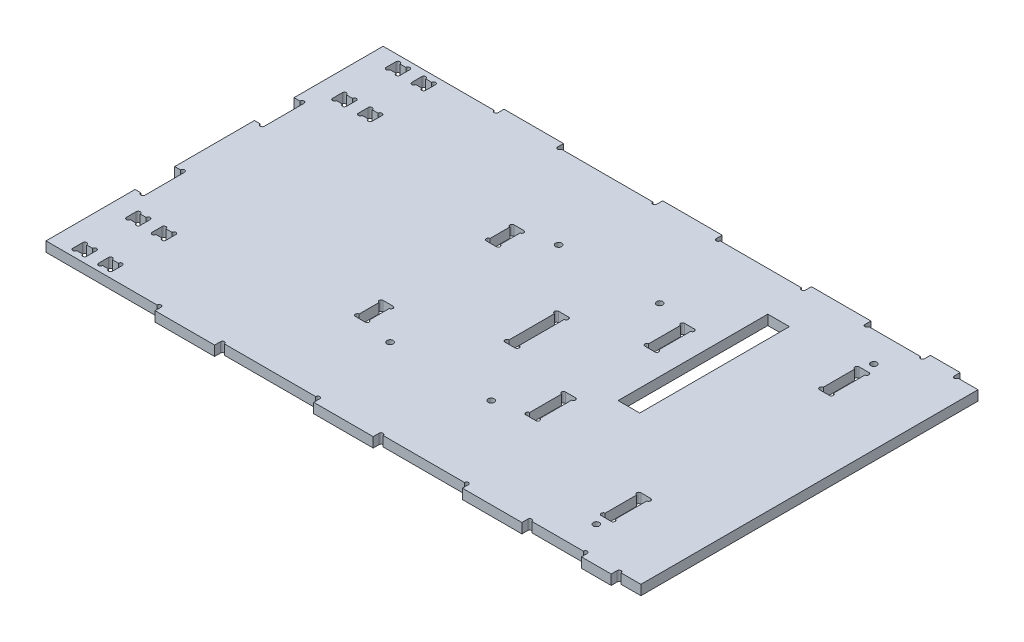
SolidWorks part; units mm, degrees
ref_plane "정면" through (0, 0, 0) normal (0, 0, 1) x (1, 0, 0)
ref_plane "윗면" through (0, 0, 0) normal (0, 1, 0) x (1, 0, 0)
ref_plane "우측면" through (0, 0, 0) normal (1, 0, 0) x (0, 0, -1)
sketch "스케치1" plane through (0, 0, 0) normal (0, 1, 0) x (1, 0, 0)
  line L1 (0, 0) -> (300, 0)
  line L2 (0, 0) -> (0, 170)
  line L3 (0, 170) -> (300, 170)
  line L4 (300, 0) -> (300, 170)
  dimension "D1" = 170
  dimension "D2" = 300
extrude "보스-돌출1" add sketch "스케치1" along normal blind 5
sketch "스케치2" plane through (0, 0, 0) normal (0, -1, 0) x (1, 0, 0)
  line L0 (160, -71.5) -> (160, 0) construction
  line L1 (160, -71.5) -> (165, -71.5)
  line L2 (160, -71.5) -> (160, -98.5)
  line L3 (160, -98.5) -> (165, -98.5)
  line L4 (165, -71.5) -> (165, -98.5)
  line L5 (0, 0) -> (300, 0) construction
  line L6 (160, -98.5) -> (160, -170) construction
  line L7 (300, -170) -> (0, -170) construction
  line L10 (300, 0) -> (300, -170) construction
  line L11 (260, 0) -> (260, -20) construction
  line L12 (260, -20) -> (265, -20)
  line L13 (260, -20) -> (260, -40)
  line L14 (260, -40) -> (265, -40)
  line L15 (265, -20) -> (265, -40)
  line L16 (260, -130) -> (265, -130)
  line L17 (260, -130) -> (260, -150)
  line L18 (260, -150) -> (265, -150)
  line L19 (265, -130) -> (265, -150)
  line L20 (260, -40) -> (260, -130) construction
  line L21 (260, -150) -> (260, -170) construction
  line L22 (265, -130) -> (265, -40) construction
  dimension "D1" = 27
  dimension "D2" = 140
  dimension "D3" = 5
  dimension "D4" = 20
  dimension "D5" = 20
  dimension "D6" = 40
  dimension "D7" = 5
extrude "컷-돌출1" cut sketch "스케치2" against normal blind 10
sketch "스케치3" plane through (0, 5, 0) normal (0, 1, 0) x (1, 0, 0)
  line L0 (183.55, 42.5) -> (180.45, 42.5) construction
  line L1 (183.55, 40) -> (183.55, 45) construction
  line L2 (180.45, 40) -> (180.45, 45) construction
  line L3 (180.45, 42.5) -> (132.55, 42.5) construction
  line L4 (132.55, 40) -> (132.55, 45) construction
  line L5 (132.55, 42.5) -> (129.45, 42.5) construction
  line L6 (129.45, 40) -> (129.45, 45) construction
  line L7 (183.55, 127.5) -> (180.45, 127.5) construction
  line L8 (183.55, 125) -> (183.55, 130) construction
  line L9 (180.45, 125) -> (180.45, 130) construction
  line L10 (180.45, 127.5) -> (132.55, 127.5) construction
  line L11 (132.55, 125) -> (132.55, 130) construction
  line L12 (132.55, 127.5) -> (129.45, 127.5) construction
  line L13 (129.45, 125) -> (129.45, 130) construction
  line L18 (262.5, 16.55) -> (262.5, 13.45) construction
  line L19 (265, 16.55) -> (260, 16.55) construction
  line L20 (265, 13.45) -> (260, 13.45) construction
  line L25 (262.5, 156.55) -> (262.5, 153.45) construction
  line L26 (265, 156.55) -> (260, 156.55) construction
  line L27 (265, 153.45) -> (260, 153.45) construction
  circle A0 centre (131, 127.5) radius 1.55
  circle A1 centre (182, 127.5) radius 1.55
  circle A2 centre (182, 42.5) radius 1.55
  circle A3 centre (131, 42.5) radius 1.55
  circle A8 centre (262.5, 155) radius 1.55
  circle A10 centre (262.5, 15) radius 1.55
  dimension "D1" = 3.1
extrude "컷-돌출2" cut sketch "스케치3" against normal blind 10
sketch "스케치4" plane through (0, 0, 0) normal (0, -1, 0) x (1, 0, 0)
  line L0 (5, -64.8) -> (0, -64.8) construction
  line L1 (5, -45) -> (0, -45) construction
  line L2 (0, -85) -> (51.0766, -85) construction
  line L3 (0, -170) -> (0, 0) construction
  line L4 (5, -105.1) -> (5, -125.1)
  line L5 (0, -64.9) -> (5, -64.9)
  line L6 (0, -64.9) -> (0, -44.9)
  line L7 (0, -44.9) -> (5, -44.9)
  line L8 (5, -64.9) -> (5, -44.9)
  line L9 (0, -125.1) -> (5, -125.1)
  line L10 (0, -105.1) -> (0, -125.1)
  line L11 (0, -105.1) -> (5, -105.1)
  dimension "D1" = 0.1
  dimension "D2" = 0.1
  dimension "D3" = 5
extrude "컷-돌출3" cut sketch "스케치4" against normal blind 5
sketch "스케치5" plane through (0, 0, 0) normal (0, -1, 0) x (1, 0, 0)
  line L0 (160, -71.5) -> (160, -98.5) construction
  line L1 (165, -98.5) -> (165, -71.5) construction
  line L2 (5, -44.9) -> (0, -44.9) construction
  line L3 (0, -64.9) -> (5, -64.9) construction
  line L12 (260, -20) -> (260, -40) construction
  line L13 (265, -40) -> (265, -20) construction
  line L14 (300, -85) -> (0, -85) construction
  line L15 (300, 0) -> (300, -170) construction
  line L16 (0, -105.1) -> (0, -64.9) construction
  circle A0 centre (160, -72.55) radius 1.05
  circle A1 centre (3.95, -44.9) radius 1.05
  circle A2 centre (3.95, -64.9) radius 1.05
  circle A3 centre (165, -72.55) radius 1.05
  circle A4 centre (260, -21.05) radius 1.05
  circle A5 centre (265, -38.95) radius 1.05
  circle A6 centre (260, -38.95) radius 1.05
  circle A7 centre (265, -21.05) radius 1.05
  circle A8 centre (265, -148.95) radius 1.05
  circle A9 centre (260, -131.05) radius 1.05
  circle A10 centre (265, -131.05) radius 1.05
  circle A11 centre (260, -148.95) radius 1.05
  circle A12 centre (165, -97.45) radius 1.05
  circle A13 centre (3.95, -105.1) radius 1.05
  circle A14 centre (3.95, -125.1) radius 1.05
  circle A15 centre (160, -97.45) radius 1.05
  dimension "D1" = 2.1
extrude "컷-돌출4" cut sketch "스케치5" against normal blind 10
sketch "스케치8" plane through (0, 0, 0) normal (0, -1, 0) x (1, 0, 0)
  line L0 (0, 0) -> (300, 0) construction
  line L1 (58, 0) -> (88, 0)
  line L2 (58, 0) -> (58, 3)
  line L3 (58, 3) -> (88, 3)
  line L4 (88, 0) -> (88, 3)
  line L5 (0, 3) -> (57.9, 3) construction
  line L6 (0, 0) -> (300, 0) construction
  line L7 (138, 3) -> (168, 3)
  line L8 (138, 3) -> (138, 0)
  line L9 (138, 0) -> (168, 0)
  line L10 (168, 3) -> (168, 0)
  line L11 (0, 0) -> (300, 0) construction
  line L12 (213, 3) -> (243, 3)
  line L13 (213, 3) -> (213, 0)
  line L14 (213, 0) -> (243, 0)
  line L15 (243, 3) -> (243, 0)
  line L16 (0, 0) -> (300, 0) construction
  line L17 (273, 3) -> (288, 3)
  line L18 (273, 3) -> (273, 0)
  line L19 (273, 0) -> (288, 0)
  line L20 (288, 3) -> (288, 0)
  line L21 (300, 0) -> (300, -170) construction
  line L22 (0, -85) -> (300, -85) construction
  line L23 (0, -105.1) -> (0, -64.9) construction
  line L24 (288, -173) -> (288, -170)
  line L25 (273, -170) -> (288, -170)
  line L26 (273, -173) -> (273, -170)
  line L27 (273, -173) -> (288, -173)
  line L28 (243, -173) -> (243, -170)
  line L29 (213, -170) -> (243, -170)
  line L30 (213, -173) -> (213, -170)
  line L31 (213, -173) -> (243, -173)
  line L32 (168, -173) -> (168, -170)
  line L33 (138, -170) -> (168, -170)
  line L34 (138, -173) -> (138, -170)
  line L35 (138, -173) -> (168, -173)
  line L36 (88, -170) -> (88, -173)
  line L37 (58, -173) -> (88, -173)
  line L38 (58, -170) -> (58, -173)
  line L39 (58, -170) -> (88, -170)
  dimension "D1" = 12
  dimension "D2" = 15
  dimension "D3" = 30
  dimension "D4" = 30
  dimension "D5" = 45
  dimension "D6" = 30
  dimension "D7" = 50
  dimension "D8" = 30
extrude "보스-돌출2" add sketch "스케치8" against normal blind 5
sketch "스케치9" plane through (0, 0, 0) normal (0, -1, 0) x (1, 0, 0)
  line L0 (0, 0) -> (58, 0) construction
  line L1 (88, 0) -> (138, 0) construction
  line L2 (88, 0) -> (138, 0) construction
  line L3 (168, 0) -> (213, 0) construction
  line L4 (168, 0) -> (213, 0) construction
  line L5 (243, 0) -> (273, 0) construction
  line L6 (243, 0) -> (273, 0) construction
  line L7 (288, 0) -> (300, 0) construction
  line L8 (0, -85) -> (300, -85) construction
  line L9 (0, -105.1) -> (0, -64.9) construction
  line L10 (300, 0) -> (300, -170) construction
  circle A0 centre (57, 0) radius 1
  circle A1 centre (89, 0) radius 1
  circle A2 centre (137, 0) radius 1
  circle A3 centre (169, 0) radius 1
  circle A4 centre (212, 0) radius 1
  circle A5 centre (272, 0) radius 1
  circle A6 centre (244, 0) radius 1
  circle A7 centre (289, 0) radius 1
  circle A8 centre (289, -170) radius 1
  circle A9 centre (244, -170) radius 1
  circle A10 centre (272, -170) radius 1
  circle A11 centre (212, -170) radius 1
  circle A12 centre (169, -170) radius 1
  circle A13 centre (137, -170) radius 1
  circle A14 centre (89, -170) radius 1
  circle A15 centre (57, -170) radius 1
  dimension "D1" = 2
extrude "컷-돌출6" cut sketch "스케치9" against normal blind 5
sketch "스케치13" plane through (0, 5, 0) normal (0, 1, 0) x (1, 0, 0)
  line L0 (30, 8.5) -> (30, 30.5) construction
  line L1 (30, 8.5) -> (23, 8.5)
  line L2 (30, 8.5) -> (30, 3.5)
  line L3 (30, 3.5) -> (23, 3.5)
  line L4 (23, 8.5) -> (23, 3.5)
  line L5 (17, 8.5) -> (10, 8.5)
  line L6 (17, 8.5) -> (17, 3.5)
  line L7 (17, 3.5) -> (10, 3.5)
  line L8 (10, 8.5) -> (10, 3.5)
  line L9 (30, 19.5) -> (11.9274, 19.5) construction
  line L10 (10, 30.5) -> (10, 35.5)
  line L11 (17, 35.5) -> (10, 35.5)
  line L12 (17, 30.5) -> (17, 35.5)
  line L13 (17, 30.5) -> (10, 30.5)
  line L14 (23, 30.5) -> (23, 35.5)
  line L15 (30, 35.5) -> (23, 35.5)
  line L16 (30, 30.5) -> (30, 35.5)
  line L17 (30, 30.5) -> (23, 30.5)
  line L18 (0, 85) -> (49.672, 85) construction
  line L19 (0, 105.1) -> (0, 64.9) construction
  line L20 (30, 150.5) -> (11.9274, 150.5) construction
  line L21 (30, 161.5) -> (30, 139.5) construction
  line L22 (30, 139.5) -> (23, 139.5)
  line L23 (30, 139.5) -> (30, 134.5)
  line L24 (30, 134.5) -> (23, 134.5)
  line L25 (23, 139.5) -> (23, 134.5)
  line L26 (17, 139.5) -> (10, 139.5)
  line L27 (17, 139.5) -> (17, 134.5)
  line L28 (17, 134.5) -> (10, 134.5)
  line L29 (10, 139.5) -> (10, 134.5)
  line L30 (10, 161.5) -> (10, 166.5)
  line L31 (17, 166.5) -> (10, 166.5)
  line L32 (17, 161.5) -> (17, 166.5)
  line L33 (17, 161.5) -> (10, 161.5)
  line L34 (23, 161.5) -> (23, 166.5)
  line L35 (30, 166.5) -> (23, 166.5)
  line L36 (30, 161.5) -> (30, 166.5)
  line L37 (30, 161.5) -> (23, 161.5)
extrude "컷-돌출9" cut sketch "스케치13" against normal blind 10
sketch "스케치14" plane through (0, 0, 0) normal (0, -1, 0) x (1, 0, 0)
  line L0 (10, -8.5) -> (17, -8.5) construction
  line L1 (17, -3.5) -> (10, -3.5) construction
  line L2 (17, -30.5) -> (23, -30.5) construction
  line L3 (23, -30.5) -> (23, -8.5) construction
  line L4 (23, -8.5) -> (17, -8.5) construction
  line L5 (17, -8.5) -> (17, -30.5) construction
  line L6 (20, -30.5) -> (20, -8.5) construction
  line L7 (17, -19.5) -> (23, -19.5) construction
  line L8 (0, -85) -> (55.1733, -85) construction
  line L9 (0, -105.1) -> (0, -64.9) construction
  line L10 (17, -150.5) -> (23, -150.5) construction
  line L11 (20, -139.5) -> (20, -161.5) construction
  line L12 (17, -161.5) -> (17, -139.5) construction
  line L13 (23, -161.5) -> (17, -161.5) construction
  line L14 (23, -139.5) -> (23, -161.5) construction
  line L15 (17, -139.5) -> (23, -139.5) construction
  circle A0 centre (11, -8.5) radius 1
  circle A1 centre (11, -3.5) radius 1
  circle A2 centre (16, -3.5) radius 1
  circle A3 centre (16, -8.5) radius 1
  circle A4 centre (24, -8.5) radius 1
  circle A5 centre (24, -3.5) radius 1
  circle A6 centre (29, -3.5) radius 1
  circle A7 centre (29, -8.5) radius 1
  circle A8 centre (29, -30.5) radius 1
  circle A9 centre (29, -35.5) radius 1
  circle A10 centre (24, -35.5) radius 1
  circle A11 centre (24, -30.5) radius 1
  circle A12 centre (16, -30.5) radius 1
  circle A13 centre (16, -35.5) radius 1
  circle A14 centre (11, -35.5) radius 1
  circle A15 centre (11, -30.5) radius 1
  circle A16 centre (11, -139.5) radius 1
  circle A17 centre (11, -134.5) radius 1
  circle A18 centre (16, -134.5) radius 1
  circle A19 centre (16, -139.5) radius 1
  circle A20 centre (24, -139.5) radius 1
  circle A21 centre (24, -134.5) radius 1
  circle A22 centre (29, -134.5) radius 1
  circle A23 centre (29, -139.5) radius 1
  circle A24 centre (29, -161.5) radius 1
  circle A25 centre (29, -166.5) radius 1
  circle A26 centre (24, -166.5) radius 1
  circle A27 centre (24, -161.5) radius 1
  circle A28 centre (16, -161.5) radius 1
  circle A29 centre (16, -166.5) radius 1
  circle A30 centre (11, -166.5) radius 1
  circle A31 centre (11, -161.5) radius 1
  dimension "D1" = 2
extrude "컷-돌출10" cut sketch "스케치14" against normal blind 10
sketch "스케치15" plane through (0, 5, 0) normal (0, 1, 0) x (1, 0, 0)
  line L1 (111, 125) -> (116, 125)
  line L2 (111, 125) -> (111, 111)
  line L3 (111, 111) -> (116, 111)
  line L4 (116, 125) -> (116, 111)
  line L5 (111, 45) -> (116, 45)
  line L6 (111, 45) -> (111, 59)
  line L7 (111, 59) -> (116, 59)
  line L8 (116, 45) -> (116, 59)
  line L9 (197, 65) -> (202, 65)
  line L10 (197, 65) -> (197, 45)
  line L11 (197, 45) -> (202, 45)
  line L12 (202, 65) -> (202, 45)
  line L13 (197, 105) -> (202, 105)
  line L14 (197, 105) -> (197, 125)
  line L15 (197, 125) -> (202, 125)
  line L16 (202, 105) -> (202, 125)
  arc A0 (116, 56.5) -> (116, 59) centre (116, 57.75) ccw construction
  dimension "D1" = 5
extrude "컷-돌출11" cut sketch "스케치15" against normal blind 10
sketch "스케치16" plane through (0, 5, 0) normal (0, 1, 0) x (1, 0, 0)
  line L0 (111, 59) -> (111, 45) construction
  line L1 (116, 45) -> (116, 59) construction
  line L2 (111, 125) -> (111, 111) construction
  line L3 (116, 111) -> (116, 125) construction
  line L4 (202, 105) -> (202, 125) construction
  line L5 (197, 125) -> (197, 105) construction
  line L6 (197, 65) -> (197, 45) construction
  line L7 (202, 45) -> (202, 65) construction
  circle A0 centre (111, 46) radius 1
  circle A1 centre (116, 46) radius 1
  circle A2 centre (116, 58) radius 1
  circle A3 centre (111, 58) radius 1
  circle A4 centre (111, 112) radius 1
  circle A5 centre (116, 112) radius 1
  circle A6 centre (116, 124) radius 1
  circle A7 centre (111, 124) radius 1
  circle A8 centre (202, 124) radius 1
  circle A10 centre (197, 124) radius 1
  circle A11 centre (197, 64) radius 1
  circle A12 centre (202, 64) radius 1
  circle A13 centre (202, 106) radius 1
  circle A14 centre (197, 106) radius 1
  circle A15 centre (197, 46) radius 1
  circle A16 centre (202, 46) radius 1
  dimension "D1" = 2
extrude "컷-돌출12" cut sketch "스케치16" against normal blind 10
sketch "스케치17" plane through (0, 5, 0) normal (0, 1, 0) x (1, 0, 0)
  line L0 (219, 97.5569) -> (219, 95.1974) construction
  line L1 (214, 74.5) -> (224.9, 74.5)
  line L2 (214, 74.5) -> (214, 150)
  line L3 (214, 150) -> (224.9, 150)
  line L4 (224.9, 74.5) -> (224.9, 150)
  line L6 (219.9, 97.5569) -> (219.9, 95.1974) construction
  line L7 (2.5, -5.5) -> (297.5, -5.5) construction
  line L8 (211, 170) -> (170, 170) construction
  dimension "D1" = 5
  dimension "D2" = 5
  dimension "D3" = 80
  dimension "D4" = 20
extrude "컷-돌출13" cut sketch "스케치17" against normal blind 10
sketch "스케치7" plane through (0, 0, 0) normal (0, -1, 0) x (1, 0, 0)
  line L0 (115.0287, -170) -> (111.9287, -170)
  line L1 (115.0287, -162) -> (116.2287, -162)
  line L2 (115.0287, -159.2) -> (115.0287, -158)
  line L3 (111.9287, -159.2) -> (111.9287, -158)
  line L4 (111.9287, -159.2) -> (110.7287, -159.2)
  line L5 (111.9287, -170) -> (111.9287, -162)
  line L6 (110.7287, -162) -> (111.9287, -162)
  line L7 (115.0287, -170) -> (115.0287, -162)
  line L8 (116.2287, -159.2) -> (115.0287, -159.2)
  line L9 (115.0287, -159.2) -> (111.9287, -159.2) construction
  line L10 (115.0287, -159.2) -> (115.0287, -162) construction
  line L11 (111.9287, -162) -> (111.9287, -159.2) construction
  line L12 (115.0287, -158) -> (111.9287, -158) construction
  line L13 (113.4787, -158) -> (113.4787, -155.529) construction
  line L14 (110.7287, -159.2) -> (110.7287, -162) construction
  line L15 (116.2287, -162) -> (116.2287, -159.2) construction
  line L16 (115.0287, -162) -> (111.9287, -162) construction
  line L17 (185.0287, -170) -> (181.9287, -170)
  line L18 (185.0287, -162) -> (186.2287, -162)
  line L19 (185.0287, -159.2) -> (185.0287, -158)
  line L20 (181.9287, -159.2) -> (181.9287, -158)
  line L21 (181.9287, -159.2) -> (180.7287, -159.2)
  line L22 (181.9287, -170) -> (181.9287, -162)
  line L23 (180.7287, -162) -> (181.9287, -162)
  line L24 (185.0287, -170) -> (185.0287, -162)
  line L25 (186.2287, -159.2) -> (185.0287, -159.2)
  line L26 (185.0287, -159.2) -> (181.9287, -159.2) construction
  line L27 (185.0287, -159.2) -> (185.0287, -162) construction
  line L28 (181.9287, -162) -> (181.9287, -159.2) construction
  line L29 (185.0287, -158) -> (181.9287, -158) construction
  line L30 (45.0287, -159.2) -> (41.9287, -159.2) construction
  line L31 (45.0287, -159.2) -> (45.0287, -162) construction
  line L32 (41.9287, -162) -> (41.9287, -159.2) construction
  line L33 (45.0287, -158) -> (41.9287, -158) construction
  line L34 (43.4787, -158) -> (43.4787, -155.529) construction
  line L35 (183.4787, -158) -> (183.4787, -155.529) construction
  line L36 (180.7287, -159.2) -> (180.7287, -162) construction
  line L37 (186.2287, -162) -> (186.2287, -159.2) construction
  line L38 (185.0287, -162) -> (181.9287, -162) construction
  line L39 (255.0287, -170) -> (251.9287, -170)
  line L40 (255.0287, -162) -> (256.2287, -162)
  line L41 (255.0287, -159.2) -> (255.0287, -158)
  line L42 (251.9287, -159.2) -> (251.9287, -158)
  line L43 (251.9287, -159.2) -> (250.7287, -159.2)
  line L44 (251.9287, -170) -> (251.9287, -162)
  line L45 (250.7287, -162) -> (251.9287, -162)
  line L46 (255.0287, -170) -> (255.0287, -162)
  line L47 (256.2287, -159.2) -> (255.0287, -159.2)
  line L48 (255.0287, -159.2) -> (251.9287, -159.2) construction
  line L49 (255.0287, -159.2) -> (255.0287, -162) construction
  line L50 (251.9287, -162) -> (251.9287, -159.2) construction
  line L51 (255.0287, -158) -> (251.9287, -158) construction
  line L52 (253.4787, -158) -> (253.4787, -155.529) construction
  line L53 (250.7287, -159.2) -> (250.7287, -162) construction
  line L54 (256.2287, -162) -> (256.2287, -159.2) construction
  line L55 (255.0287, -162) -> (251.9287, -162) construction
  line L56 (45.0287, -8) -> (41.9287, -8) construction
  line L57 (46.2287, -8) -> (46.2287, -10.8) construction
  line L58 (40.7287, -10.8) -> (40.7287, -8) construction
  line L59 (255.0287, -8) -> (251.9287, -8) construction
  line L60 (256.2287, -8) -> (256.2287, -10.8) construction
  line L61 (250.7287, -10.8) -> (250.7287, -8) construction
  line L62 (253.4787, -12) -> (253.4787, -14.471) construction
  line L63 (255.0287, -12) -> (251.9287, -12) construction
  line L64 (251.9287, -8) -> (251.9287, -10.8) construction
  line L65 (255.0287, -10.8) -> (255.0287, -8) construction
  line L66 (255.0287, -10.8) -> (251.9287, -10.8) construction
  line L67 (185.0287, -8) -> (181.9287, -8) construction
  line L68 (186.2287, -8) -> (186.2287, -10.8) construction
  line L69 (40.7287, -159.2) -> (40.7287, -162) construction
  line L71 (180.7287, -10.8) -> (180.7287, -8) construction
  line L72 (183.4787, -12) -> (183.4787, -14.471) construction
  line L73 (43.4787, -12) -> (43.4787, -14.471) construction
  line L74 (45.0287, -12) -> (41.9287, -12) construction
  line L75 (0, -85) -> (300, -85) construction
  line L76 (0, -105.1) -> (0, -64.9) construction
  line L77 (300, 0) -> (300, -170) construction
  line L78 (46.2287, -162) -> (46.2287, -159.2) construction
  line L79 (45.0287, -162) -> (41.9287, -162) construction
  line L80 (41.9287, -8) -> (41.9287, -10.8) construction
  line L81 (45.0287, -10.8) -> (45.0287, -8) construction
  line L82 (45.0287, -10.8) -> (41.9287, -10.8) construction
  line L83 (185.0287, -12) -> (181.9287, -12) construction
  line L84 (181.9287, -8) -> (181.9287, -10.8) construction
  line L85 (185.0287, -10.8) -> (185.0287, -8) construction
  line L86 (185.0287, -10.8) -> (181.9287, -10.8) construction
  line L87 (115.0287, -8) -> (111.9287, -8) construction
  line L88 (116.2287, -8) -> (116.2287, -10.8) construction
  line L89 (110.7287, -10.8) -> (110.7287, -8) construction
  line L90 (113.4787, -12) -> (113.4787, -14.471) construction
  line L91 (115.0287, -12) -> (111.9287, -12) construction
  line L92 (111.9287, -8) -> (111.9287, -10.8) construction
  line L93 (115.0287, -10.8) -> (115.0287, -8) construction
  line L94 (115.0287, -10.8) -> (111.9287, -10.8) construction
  line L95 (46.2287, -10.8) -> (45.0287, -10.8)
  line L96 (45.0287, 0) -> (45.0287, -8)
  line L97 (45.0287, -170) -> (41.9287, -170)
  line L98 (45.0287, -162) -> (46.2287, -162)
  line L99 (45.0287, -159.2) -> (45.0287, -158)
  line L100 (41.9287, -159.2) -> (41.9287, -158)
  line L101 (41.9287, -159.2) -> (40.7287, -159.2)
  line L102 (41.9287, -170) -> (41.9287, -162)
  line L103 (40.7287, -162) -> (41.9287, -162)
  line L104 (45.0287, -170) -> (45.0287, -162)
  line L105 (46.2287, -159.2) -> (45.0287, -159.2)
  line L106 (325.0287, -170) -> (321.9287, -170) [skipped]
  line L107 (325.0287, -162) -> (326.2287, -162) [skipped]
  line L108 (325.0287, -159.2) -> (325.0287, -158) [skipped]
  line L109 (321.9287, -159.2) -> (321.9287, -158) [skipped]
  line L110 (321.9287, -159.2) -> (320.7287, -159.2) [skipped]
  line L111 (321.9287, -170) -> (321.9287, -162) [skipped]
  line L112 (320.7287, -162) -> (321.9287, -162) [skipped]
  line L113 (325.0287, -170) -> (325.0287, -162) [skipped]
  line L114 (326.2287, -159.2) -> (325.0287, -159.2) [skipped]
  line L115 (325.0287, -159.2) -> (321.9287, -159.2) construction
  line L116 (325.0287, -159.2) -> (325.0287, -162) construction
  line L117 (321.9287, -162) -> (321.9287, -159.2) construction
  line L118 (325.0287, -158) -> (321.9287, -158) construction
  line L119 (323.4787, -158) -> (323.4787, -155.529) construction
  line L120 (320.7287, -159.2) -> (320.7287, -162) construction
  line L121 (326.2287, -162) -> (326.2287, -159.2) construction
  line L122 (325.0287, -162) -> (321.9287, -162) construction
  line L123 (40.7287, -8) -> (41.9287, -8)
  line L124 (41.9287, 0) -> (41.9287, -8)
  line L125 (41.9287, -10.8) -> (40.7287, -10.8)
  line L126 (41.9287, -10.8) -> (41.9287, -12)
  line L127 (45.0287, -10.8) -> (45.0287, -12)
  line L128 (45.0287, -8) -> (46.2287, -8)
  line L129 (45.0287, 0) -> (41.9287, 0)
  line L130 (256.2287, -10.8) -> (255.0287, -10.8)
  line L131 (255.0287, 0) -> (255.0287, -8)
  line L132 (250.7287, -8) -> (251.9287, -8)
  line L133 (251.9287, 0) -> (251.9287, -8)
  line L134 (251.9287, -10.8) -> (250.7287, -10.8)
  line L135 (251.9287, -10.8) -> (251.9287, -12)
  line L136 (255.0287, -10.8) -> (255.0287, -12)
  line L137 (255.0287, -8) -> (256.2287, -8)
  line L138 (255.0287, 0) -> (251.9287, 0)
  line L139 (186.2287, -10.8) -> (185.0287, -10.8)
  line L140 (185.0287, 0) -> (185.0287, -8)
  line L141 (180.7287, -8) -> (181.9287, -8)
  line L142 (181.9287, 0) -> (181.9287, -8)
  line L143 (181.9287, -10.8) -> (180.7287, -10.8)
  line L144 (181.9287, -10.8) -> (181.9287, -12)
  line L145 (185.0287, -10.8) -> (185.0287, -12)
  line L146 (185.0287, -8) -> (186.2287, -8)
  line L147 (185.0287, 0) -> (181.9287, 0)
  line L148 (116.2287, -10.8) -> (115.0287, -10.8)
  line L149 (115.0287, 0) -> (115.0287, -8)
  line L150 (110.7287, -8) -> (111.9287, -8)
  line L151 (111.9287, 0) -> (111.9287, -8)
  line L152 (111.9287, -10.8) -> (110.7287, -10.8)
  line L153 (111.9287, -10.8) -> (111.9287, -12)
  line L154 (115.0287, -10.8) -> (115.0287, -12)
  line L155 (115.0287, -8) -> (116.2287, -8)
  line L156 (115.0287, 0) -> (111.9287, 0)
  arc A0 (111.9287, -158) -> (115.0287, -158) centre (113.4787, -158) cw
  arc A1 (116.2287, -159.2) -> (116.2287, -162) centre (116.2287, -160.6) cw
  arc A2 (110.7287, -162) -> (110.7287, -159.2) centre (110.7287, -160.6) cw
  arc A3 (181.9287, -158) -> (185.0287, -158) centre (183.4787, -158) cw
  arc A4 (186.2287, -159.2) -> (186.2287, -162) centre (186.2287, -160.6) cw
  arc A5 (180.7287, -162) -> (180.7287, -159.2) centre (180.7287, -160.6) cw
  arc A6 (251.9287, -158) -> (255.0287, -158) centre (253.4787, -158) cw
  arc A7 (256.2287, -159.2) -> (256.2287, -162) centre (256.2287, -160.6) cw
  arc A8 (250.7287, -162) -> (250.7287, -159.2) centre (250.7287, -160.6) cw
  arc A9 (40.7287, -8) -> (40.7287, -10.8) centre (40.7287, -9.4) ccw
  arc A10 (46.2287, -10.8) -> (46.2287, -8) centre (46.2287, -9.4) ccw
  arc A11 (41.9287, -12) -> (45.0287, -12) centre (43.4787, -12) ccw
  arc A12 (250.7287, -8) -> (250.7287, -10.8) centre (250.7287, -9.4) ccw
  arc A13 (41.9287, -158) -> (45.0287, -158) centre (43.4787, -158) cw
  arc A14 (46.2287, -159.2) -> (46.2287, -162) centre (46.2287, -160.6) cw
  arc A15 (40.7287, -162) -> (40.7287, -159.2) centre (40.7287, -160.6) cw
  arc A16 (321.9287, -158) -> (325.0287, -158) centre (323.4787, -158) cw [skipped]
  arc A17 (326.2287, -159.2) -> (326.2287, -162) centre (326.2287, -160.6) cw [skipped]
  arc A18 (320.7287, -162) -> (320.7287, -159.2) centre (320.7287, -160.6) cw [skipped]
  arc A19 (256.2287, -10.8) -> (256.2287, -8) centre (256.2287, -9.4) ccw
  arc A20 (251.9287, -12) -> (255.0287, -12) centre (253.4787, -12) ccw
  arc A21 (180.7287, -8) -> (180.7287, -10.8) centre (180.7287, -9.4) ccw
  arc A22 (186.2287, -10.8) -> (186.2287, -8) centre (186.2287, -9.4) ccw
  arc A23 (181.9287, -12) -> (185.0287, -12) centre (183.4787, -12) ccw
  arc A24 (110.7287, -8) -> (110.7287, -10.8) centre (110.7287, -9.4) ccw
  arc A25 (116.2287, -10.8) -> (116.2287, -8) centre (116.2287, -9.4) ccw
  arc A26 (111.9287, -12) -> (115.0287, -12) centre (113.4787, -12) ccw
  dimension "D1" = 5
  dimension "D2" = 8
extrude "컷-돌출5" [suppressed] cut sketch "스케치7" against normal blind 10
sketch "스케치18" plane through (0, 0, 0) normal (0, -1, 0) x (1, 0, 0)
  line L0 (0, -85) -> (300, -85) construction
  line L1 (0, -105.1) -> (0, -64.9) construction
  line L2 (300, 0) -> (300, -170) construction
  line L4 (285, -152.5) -> (15, -152.5) construction
  line L5 (285, -152.5) -> (285, -17.5) construction
  line L6 (285, -17.5) -> (15, -17.5) construction
  line L7 (15, -152.5) -> (15, -17.5) construction
  line L8 (285, -152.5) -> (15, -17.5) construction
  line L9 (285, -17.5) -> (15, -152.5) construction
  circle A0 centre (15, -17.5) radius 6
  circle A1 centre (15, -152.5) radius 6
  circle A2 centre (285, -17.5) radius 6
  circle A3 centre (285, -152.5) radius 6
  point P6 (150, -85)
  dimension "D3" = 12
  dimension "D1" = 135
  dimension "D2" = 270
extrude "컷-돌출14" [suppressed] cut sketch "스케치18" against normal blind 1.5
sketch "스케치19" plane through (0, 5, 0) normal (0, 1, 0) x (1, 0, 0)
  line L0 (111, 123) -> (111, 113) construction
  line L1 (110.9, 123.914) -> (116.1, 123.914)
  line L2 (110.9, 123.914) -> (110.9, 112.1352)
  line L3 (110.9, 112.1352) -> (116.1, 112.1352)
  line L4 (116.1, 123.914) -> (116.1, 112.1352)
  line L5 (110.9, 57.988) -> (116.1, 57.988)
  line L6 (110.9, 57.988) -> (110.9, 46.2932)
  line L7 (110.9, 46.2932) -> (116.1, 46.2932)
  line L8 (116.1, 57.988) -> (116.1, 46.2932)
  line L9 (196.9, 63.9937) -> (202.1, 63.9937)
  line L10 (196.9, 63.9937) -> (196.9, 46.6181)
  line L11 (196.9, 46.6181) -> (202.1, 46.6181)
  line L12 (202.1, 63.9937) -> (202.1, 46.6181)
  line L13 (196.9, 123.914) -> (202.1, 123.914)
  line L14 (196.9, 123.914) -> (196.9, 106.2522)
  line L15 (196.9, 106.2522) -> (202.1, 106.2522)
  line L16 (202.1, 123.914) -> (202.1, 106.2522)
  line L17 (116, 113) -> (116, 123) construction
  line L18 (111, 57) -> (111, 47) construction
  line L19 (116, 47) -> (116, 57) construction
  line L20 (197, 63) -> (197, 47) construction
  line L21 (202, 47) -> (202, 63) construction
  line L22 (197, 123) -> (197, 107) construction
  line L23 (202, 107) -> (202, 123) construction
  line L24 (260, 132.1) -> (260, 147.9) construction
  line L25 (259.9, 21.181) -> (265.1, 21.181)
  line L26 (259.9, 21.181) -> (259.9, 38.6155)
  line L27 (259.9, 38.6155) -> (265.1, 38.6155)
  line L28 (265.1, 21.181) -> (265.1, 38.6155)
  line L29 (259.9, 131.2347) -> (265.1, 131.2347)
  line L30 (259.9, 131.2347) -> (259.9, 149.0422)
  line L31 (259.9, 149.0422) -> (265.1, 149.0422)
  line L32 (265.1, 131.2347) -> (265.1, 149.0422)
  line L33 (265, 147.9) -> (265, 132.1) construction
  line L34 (260, 22.1) -> (260, 37.9) construction
  line L35 (265, 37.9) -> (265, 22.1) construction
  dimension "D1" = 0.1
  dimension "D2" = 0.1
  dimension "D3" = 0.1
  dimension "D4" = 0.1
  dimension "D5" = 0.1
  dimension "D6" = 0.1
  dimension "D7" = 0.1
  dimension "D8" = 0.1
  dimension "D9" = 0.1
  dimension "D10" = 0.1
  dimension "D11" = 0.1
  dimension "D12" = 0.1
extrude "컷-돌출15" cut sketch "스케치19" against normal blind 10
